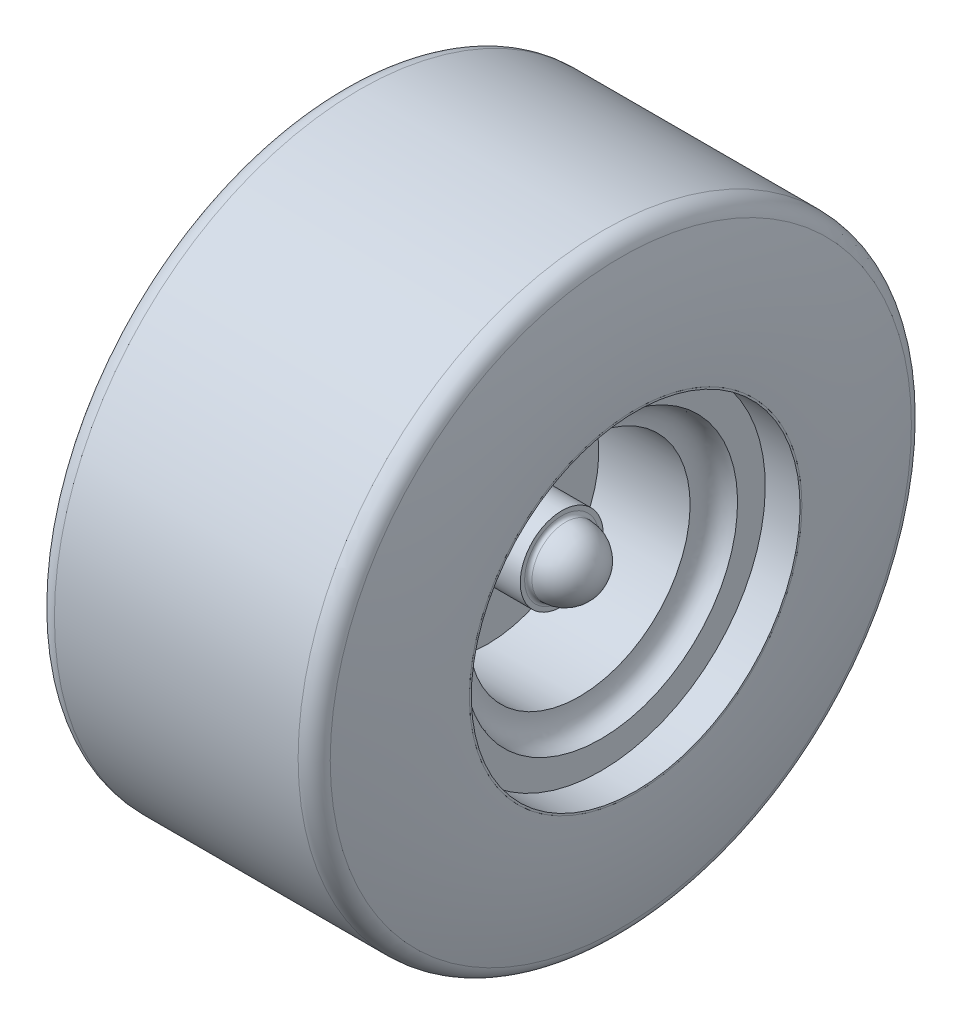
SolidWorks part; units mm, degrees
ref_plane "Front Plane" through (0, 0, 0) normal (0, 0, 1) x (1, 0, 0)
ref_plane "Top Plane" through (0, 0, 0) normal (0, 1, 0) x (1, 0, 0)
ref_plane "Right Plane" through (0, 0, 0) normal (1, 0, 0) x (0, 0, -1)
sketch "Sketch1" plane through (0, 0, 0) normal (0, 0, 1) x (1, 0, 0)
  line L0 (0, 0) -> (344.299, 0) construction
  line L1 (106.3625, 76.2) -> (106.3625, 153.0743) construction
  line L2 (0, 209.55) -> (93.6625, 209.55)
  line L3 (0, 209.55) -> (0, 114.3)
  line L4 (0, 114.3) -> (106.3625, 114.3)
  spline S0 degree 2 poles (93.6625, 209.55) (106.3625, 162.3465) (106.3625, 114.3) knots 0 0 0 1 1 1
  dimension "D1" = 419.1
  dimension "D2" = 93.6625
  dimension "D3" = 228.6
  dimension "D4" = 12.7
revolve "Revolve1" add sketch "Sketch1" angle 360 about L0
mirror "Mirror1" of "Revolve1"
sketch "Sketch2" plane through (0, 0, 0) normal (0, 0, 1) x (1, 0, 0)
  line L0 (-17.4625, 0) -> (-17.4625, 96.9152)
  line L1 (0, 0) -> (-87.628, 0) construction
  line L2 (-106.3625, 114.3) -> (-106.3625, -114.3) construction
  line L3 (-106.3625, 114.3) -> (-106.3625, 113.03)
  line L4 (-106.3625, 113.03) -> (-101.7607, 113.03)
  line L5 (-90.2477, 96.9152) -> (-17.4625, 96.9152)
  line L6 (-106.3625, 114.3) -> (0, 114.3)
  line L7 (0, 114.3) -> (0, 0)
  line L8 (-17.4625, 0) -> (0, 0)
  line L9 (-101.7607, 113.03) -> (-90.2477, 96.9152)
  dimension "D1" = 88.9
  dimension "D2" = 1.27
revolve "Revolve2" add sketch "Sketch2" angle 360 about L1
sketch "Sketch3" plane through (0, 0, 0) normal (0, 0, 1) x (1, 0, 0)
  line L0 (106.3625, 114.3) -> (0, 114.3)
  line L1 (0, 114.3) -> (0, 0)
  line L2 (106.3625, 114.3) -> (106.3625, 113.03)
  line L3 (106.3625, 114.3) -> (106.3625, -114.3) construction
  line L4 (106.3625, 113.03) -> (82.4395, 113.03)
  line L5 (82.4395, 113.03) -> (82.4395, 93.98)
  line L6 (67.5832, 76.2) -> (4.7625, 76.2)
  line L7 (4.7625, 76.2) -> (4.7625, 0)
  line L8 (4.7625, 0) -> (0, 0)
  line L9 (4.7625, 0) -> (106.3625, 0) construction
  spline S0 degree 2 poles (67.5832, 76.2) (67.3974, 92.7891) (82.4395, 93.98) knots 0 0 0 1 1 1
  dimension "D1" = 101.6
  dimension "D2" = 152.4
  dimension "D3" = 1.27
  dimension "D4" = 23.923
  dimension "D5" = 187.96
revolve "Revolve3" add sketch "Sketch3" angle 360 about L9
sketch "Sketch4" plane through (4.7625, 0, 0) normal (1, 0, 0) x (0, 0, -1)
  circle A0 centre (0, 0) radius 28.575
  dimension "D1" = 57.15
extrude "Boss-Extrude2" add sketch "Sketch4" along normal blind 50.8 separate body
sketch "Sketch6" plane through (55.5625, 0, 0) normal (1, 0, 0) x (0, 0, -1)
  circle A0 centre (0, 0) radius 23.0247
extrude "Boss-Extrude5" add sketch "Sketch6" along normal blind 2.54
dome "Dome1" faces to dome 1 distance 22.86 reverse direction no elliptical dome no face at (58.1025, 23.0247, 0) parameters "D1"=22.86
fillet "Fillet1" radius 2.54 1 edges at (55.5625, 23.0247, 0)
sketch "Sketch5" plane through (-17.4625, 0, 0) normal (-1, 0, 0) x (0, 0, 1)
  circle A0 centre (0, 0) radius 19.05
  dimension "D1" = 38.1
extrude "Boss-Extrude3" add sketch "Sketch5" along normal blind 63.5 separate body
fillet "Fillet2" radius 12.7 2 edges at (93.6625, 0, 209.55) (-93.6625, 0, 209.55)
